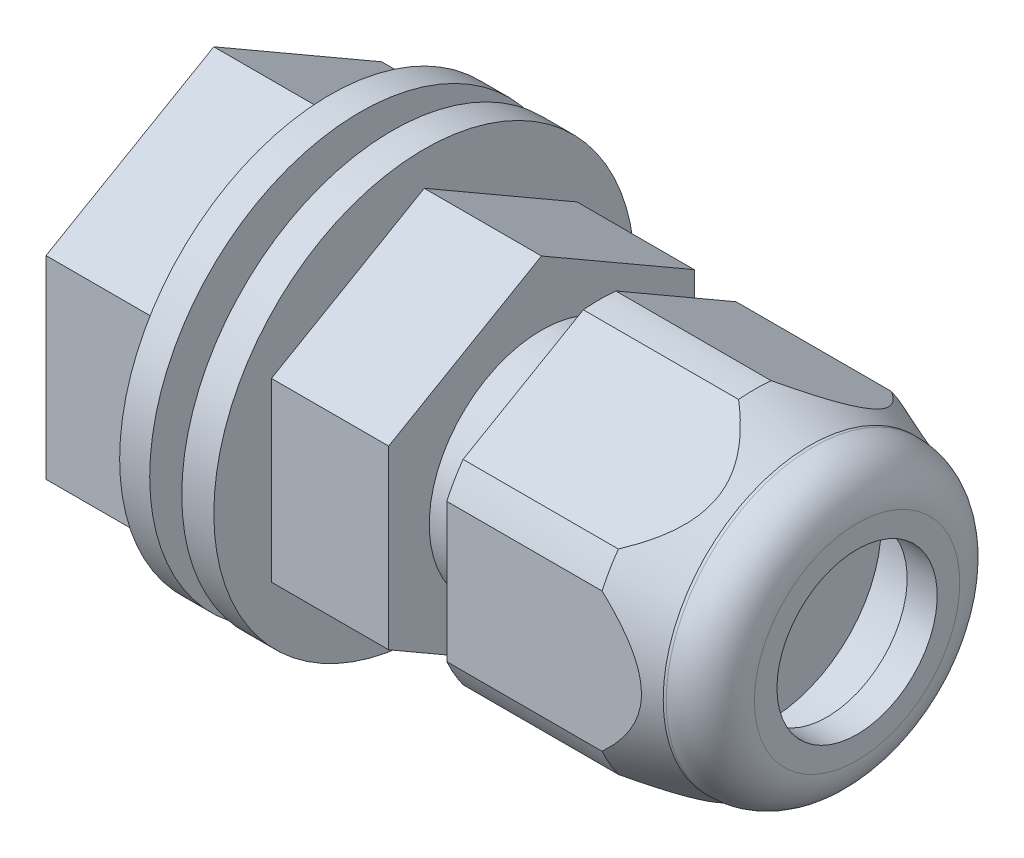
SolidWorks part; units mm, degrees
ref_plane "Front" through (0, 0, 0) normal (0, 0, 1) x (1, 0, 0)
ref_plane "Top" through (0, 0, 0) normal (0, 1, 0) x (1, 0, 0)
ref_plane "Right" through (0, 0, 0) normal (1, 0, 0) x (0, 0, -1)
sketch "Sketch1" plane through (0, 0, 0) normal (1, 0, 0) x (0, 0, -1)
  circle A0 centre (0, 0) radius 6.2
  dimension "\"c\"D1" = 12.4
extrude "Boss-Extrude1" add sketch "Sketch1" along normal blind 10.8
sketch "Sketch2" plane through (10.8, 0, 0) normal (1, 0, 0) x (0, 0, -1)
  line L1 (0, -8.8046) -> (7.625, -4.4023)
  line L2 (7.625, -4.4023) -> (7.625, 4.4023)
  line L3 (7.625, 4.4023) -> (0, 8.8046)
  line L4 (0, 8.8046) -> (-7.625, 4.4023)
  line L5 (-7.625, 4.4023) -> (-7.625, -4.4023)
  line L6 (-7.625, -4.4023) -> (0, -8.8046)
  circle A0 centre (0, 0) radius 7.625 construction
  dimension "\"hex\"D1" = 15.25
extrude "Boss-Extrude2" add sketch "Sketch2" along normal blind 5.85
sketch "Sketch3" plane through (16.65, 0, 0) normal (1, 0, 0) x (0, 0, -1)
  circle A0 centre (0, 0) radius 5.6
  dimension "\"body2\"D1" = 11.2
extrude "Boss-Extrude3" add sketch "Sketch3" along normal offset from surface (11.35 mm away) 28 up to face at (0, 0, -6.2)
sketch "Sketch4" plane through (10.8, 0, 0) normal (-1, 0, 0) x (0, 0, 1)
  circle A0 centre (0, 0) radius 10.5
  dimension "\"gasket diameter\"D1" = 21
extrude "Boss-Extrude4" add sketch "Sketch4" along normal blind 1.6
ref_plane "Plane1" through (7.6, 0, 0) normal (-1, 0, 0) x (0, 0, 1)
sketch "Sketch5" plane through (7.6, 0, 0) normal (-1, 0, 0) x (0, 0, 1)
  circle A0 centre (0, 0) radius 10.5
  dimension "\"H\"D1" = 21
extrude "Boss-Extrude5" add sketch "Sketch5" along normal blind 7.3
sketch "Sketch6" plane through (0.3, 0, 0) normal (-1, 0, 0) x (0, 0, 1)
  line L1 (0, -9.6706) -> (8.375, -4.8353)
  line L2 (8.375, -4.8353) -> (8.375, 4.8353)
  line L3 (8.375, 4.8353) -> (0, 9.6706)
  line L4 (0, 9.6706) -> (-8.375, 4.8353)
  line L5 (-8.375, 4.8353) -> (-8.375, -4.8353)
  line L6 (-8.375, -4.8353) -> (0, -9.6706)
  circle A0 centre (0, 0) radius 8.375 construction
  circle A1 centre (0, 0) radius 13.375
  dimension "\"NUT DIA\"D1" = 16.75
  dimension "D2" = 5
extrude "Cut-Extrude1" cut sketch "Sketch6" against normal offset from surface (5.8 mm away) 1.5 up to face at (7.6, 0, 10.5)
sketch "Sketch7" plane through (0, 0, 0) normal (-1, 0, 0) x (0, 0, 1)
  circle A0 centre (0, 0) radius 4
  dimension "\"B\"D1" = 8
extrude "Cut-Extrude2" cut sketch "Sketch7" against normal offset from surface (16.5 mm away) 11.5 up to face at (28, 0, -5.6)
sketch "Sketch8" plane through (28, 0, 0) normal (1, 0, 0) x (0, 0, -1)
  circle A0 centre (0, 0) radius 1.9
  dimension "\"A\"D1" = 3.8
extrude "Cut-Extrude3" cut sketch "Sketch8" against normal up to surface (11.5 mm away) up to face at (16.5, 0, -4)
sketch "Sketch9" plane through (0, 0, 0) normal (0, 0, 1) x (1, 0, 0)
  line L0 (19.55, 8.375) -> (27.3, 8.375)
  line L1 (27.3, 8.375) -> (30.05, 7.325)
  line L2 (30.05, 7.325) -> (30.2, 7.325)
  line L3 (32.4, 5.125) -> (32.4, 4)
  line L4 (19.55, 8.375) -> (19.55, 5.6)
  line L5 (28, 5.6) -> (16.65, 5.6) construction
  line L6 (19.55, 5.6) -> (30.425, 5.6)
  line L7 (30.9, 5.125) -> (30.9, 4)
  line L8 (30.9, 4) -> (32.4, 4)
  line L9 (0, 0) -> (59.2195, 0) construction
  line L11 (16.65, 4.4023) -> (16.65, 8.8046) construction
  arc A0 (32.4, 5.125) -> (30.2, 7.325) centre (30.2, 5.125) ccw
  arc A1 (30.9, 5.125) -> (30.425, 5.6) centre (30.425, 5.125) ccw
  dimension "D6" = 2.2
  dimension "\"OD COLLET\"D1" = 16.75
  dimension "\"C_LENGTH\"D2" = 15.75
  dimension "\"ID COLLET\"D3" = 8
  dimension "D4" = 10.5
  dimension "D5" = 2.9
  dimension "\"OD2\"D7" = 14.65
  dimension "D8" = 2.75
  dimension "D10" = 1.5
revolve "Revolve1" add sketch "Sketch9" angle 360 about L9
sketch "Sketch10" plane through (32.4, 0, 0) normal (1, 0, 0) x (0, 0, -1)
  line L1 (7.625, -4.4023) -> (7.625, 4.4023)
  line L2 (7.625, 4.4023) -> (0, 8.8046)
  line L3 (0, 8.8046) -> (-7.625, 4.4023)
  line L4 (-7.625, 4.4023) -> (-7.625, -4.4023)
  line L5 (-7.625, -4.4023) -> (0, -8.8046)
  line L6 (0, -8.8046) -> (7.625, -4.4023)
  circle A0 centre (0, 0) radius 7.625 construction
  circle A1 centre (0, 0) radius 12.625
  dimension "\"COLLET HEX\"D1" = 15.25
  dimension "D2" = 5
extrude "Cut-Extrude4" cut sketch "Sketch10" against normal up to surface (12.85 mm away) up to face at (19.55, 0, -5.6)
sketch "Sketch11" plane through (16.65, 0, 0) normal (1, 0, 0) x (0, 0, -1)
  point P0 (0, 0)
other "CPoint1" parameters "Diameter"=3, "StubLength"=4
ref_axis "Axis1" through (26.65, 0, 0) along (-1, 0, 0)
other "CPoint2" parameters "Diameter"=3, "StubLength"=4
ref_axis "Axis2" through (20.8, 0, 0) along (-1, 0, 0)
